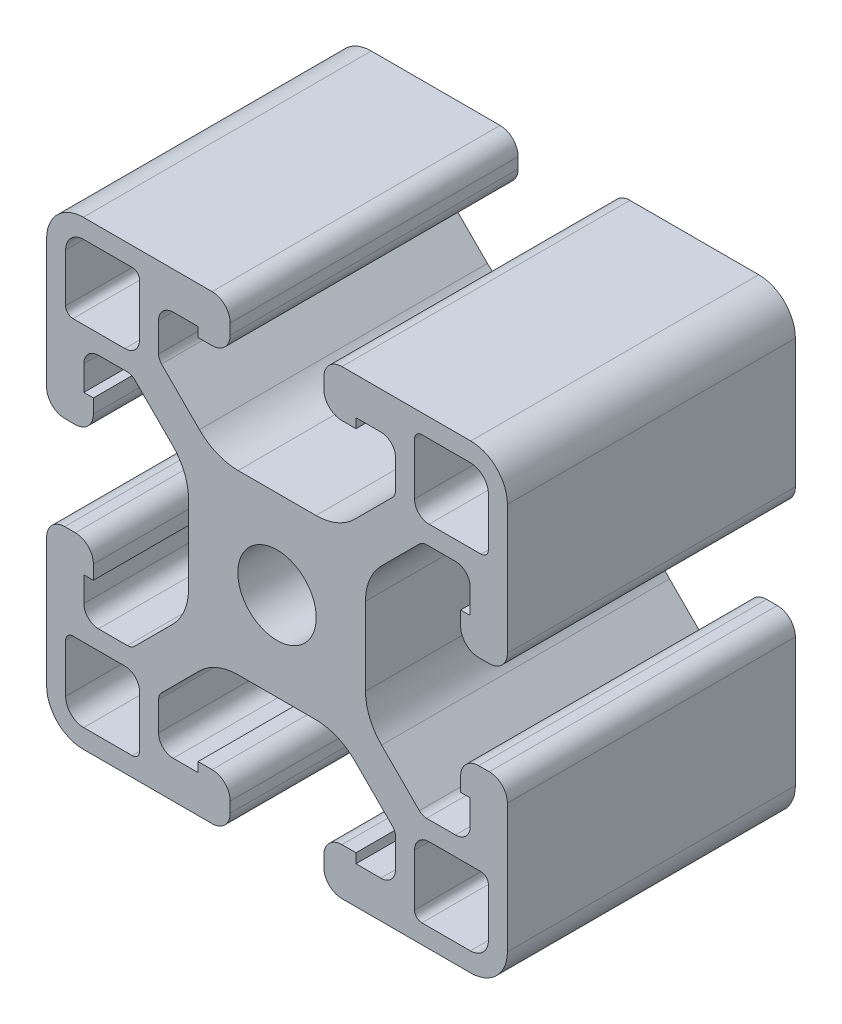
SolidWorks part; units mm, degrees
material "6005A-T61 Aluminum"
ref_plane "Front Plane" through (0, 0, 0) normal (0, 0, 1) x (1, 0, 0)
ref_plane "Top Plane" through (0, 0, 0) normal (0, 1, 0) x (1, 0, 0)
ref_plane "Right Plane" through (0, 0, 0) normal (1, 0, 0) x (0, 0, -1)
sketch "Sketch2" plane through (0, 0, 0) normal (0, 0, 1) x (1, 0, 0)
  line L0 (-16.82, 20) -> (-5.635, 20)
  line L1 (-3.379, 7.68) -> (3.379, 7.68)
  line L2 (-10.285, 12.9871) -> (-10.285, 15.5)
  line L3 (10.285, 12.9871) -> (10.285, 15.5)
  line L4 (4.065, 17.51) -> (4.065, 18.43)
  line L5 (-4.065, 17.51) -> (-4.065, 18.43)
  line L6 (-6.855, 15.94) -> (-5.635, 15.94)
  line L7 (5.635, 15.94) -> (6.855, 15.94)
  line L8 (5.635, 20) -> (16.82, 20)
  line L9 (6.855, 16.77) -> (9.015, 16.77)
  line L10 (-9.015, 16.77) -> (-6.855, 16.77)
  line L11 (-6.855, 15.94) -> (-6.855, 16.77)
  line L12 (6.855, 15.94) -> (6.855, 16.77)
  line L13 (-6.7378, 9.0712) -> (-10.0243, 12.3578)
  line L14 (6.7378, 9.0712) -> (10.0243, 12.3578)
  line L15 (-16.78, 18.35) -> (-12.575, 18.35)
  line L16 (-18.35, 16.78) -> (-18.35, 12.575)
  line L17 (-11.935, 13.205) -> (-11.935, 17.71)
  line L18 (-13.205, 11.935) -> (-17.71, 11.935)
  line L19 (-7.68, -3.379) -> (-7.68, 3.379)
  line L20 (-20, -16.82) -> (-20, -5.635)
  line L21 (-18.35, -16.78) -> (-18.35, -12.575)
  line L22 (-20, 5.635) -> (-20, 16.82)
  line L23 (-15.94, -6.855) -> (-15.94, -5.635)
  line L24 (-16.77, -9.015) -> (-16.77, -6.855)
  line L25 (-15.94, 5.635) -> (-15.94, 6.855)
  line L26 (-16.77, 6.855) -> (-16.77, 9.015)
  line L27 (-9.0712, 6.7378) -> (-12.3578, 10.0243)
  line L28 (-9.0712, -6.7378) -> (-12.3578, -10.0243)
  line L29 (-17.51, -4.065) -> (-18.43, -4.065)
  line L30 (-17.51, 4.065) -> (-18.43, 4.065)
  line L31 (-12.9871, 10.285) -> (-15.5, 10.285)
  line L32 (-15.94, 6.855) -> (-16.77, 6.855)
  line L33 (-12.9871, -10.285) -> (-15.5, -10.285)
  line L34 (-13.205, -11.935) -> (-17.71, -11.935)
  line L35 (-15.94, -6.855) -> (-16.77, -6.855)
  line L36 (-16.78, -18.35) -> (-12.575, -18.35)
  line L37 (-11.935, -13.205) -> (-11.935, -17.71)
  line L38 (3.379, -7.68) -> (-3.379, -7.68)
  line L39 (16.82, -20) -> (5.635, -20)
  line L40 (16.78, -18.35) -> (12.575, -18.35)
  line L41 (-5.635, -20) -> (-16.82, -20)
  line L42 (6.855, -15.94) -> (5.635, -15.94)
  line L43 (9.015, -16.77) -> (6.855, -16.77)
  line L44 (-5.635, -15.94) -> (-6.855, -15.94)
  line L45 (-6.855, -16.77) -> (-9.015, -16.77)
  line L46 (-6.7378, -9.0712) -> (-10.0243, -12.3578)
  line L47 (6.7378, -9.0712) -> (10.0243, -12.3578)
  line L48 (4.065, -17.51) -> (4.065, -18.43)
  line L49 (-4.065, -17.51) -> (-4.065, -18.43)
  line L50 (-10.285, -12.9871) -> (-10.285, -15.5)
  line L51 (-6.855, -15.94) -> (-6.855, -16.77)
  line L52 (10.285, -12.9871) -> (10.285, -15.5)
  line L53 (11.935, -13.205) -> (11.935, -17.71)
  line L54 (6.855, -15.94) -> (6.855, -16.77)
  line L55 (18.35, -16.78) -> (18.35, -12.575)
  line L56 (13.205, -11.935) -> (17.71, -11.935)
  line L57 (7.68, 3.379) -> (7.68, -3.379)
  line L58 (20, 16.82) -> (20, 5.635)
  line L59 (18.35, 16.78) -> (18.35, 12.575)
  line L60 (20, -5.635) -> (20, -16.82)
  line L61 (15.94, 6.855) -> (15.94, 5.635)
  line L62 (16.77, 9.015) -> (16.77, 6.855)
  line L63 (15.94, -5.635) -> (15.94, -6.855)
  line L64 (16.77, -6.855) -> (16.77, -9.015)
  line L65 (9.0712, -6.7378) -> (12.3578, -10.0243)
  line L66 (9.0712, 6.7378) -> (12.3578, 10.0243)
  line L67 (17.51, 4.065) -> (18.43, 4.065)
  line L68 (17.51, -4.065) -> (18.43, -4.065)
  line L69 (12.9871, -10.285) -> (15.5, -10.285)
  line L70 (15.94, -6.855) -> (16.77, -6.855)
  line L71 (12.9871, 10.285) -> (15.5, 10.285)
  line L72 (13.205, 11.935) -> (17.71, 11.935)
  line L73 (15.94, 6.855) -> (16.77, 6.855)
  line L74 (16.78, 18.35) -> (12.575, 18.35)
  line L75 (11.935, 13.205) -> (11.935, 17.71)
  circle A0 centre (0, 0) radius 3.405
  arc A1 (-6.7378, 9.0712) -> (-3.379, 7.68) centre (-3.379, 12.43) ccw
  arc A2 (3.379, 7.68) -> (6.7378, 9.0712) centre (3.379, 12.43) ccw
  arc A3 (10.0243, 12.3578) -> (10.285, 12.9871) centre (9.395, 12.9871) ccw
  arc A4 (-10.285, 12.9871) -> (-10.0243, 12.3578) centre (-9.395, 12.9871) ccw
  arc A5 (-9.015, 16.77) -> (-10.285, 15.5) centre (-9.015, 15.5) ccw
  arc A6 (10.285, 15.5) -> (9.015, 16.77) centre (9.015, 15.5) ccw
  arc A7 (4.065, 17.51) -> (5.635, 15.94) centre (5.635, 17.51) ccw
  arc A8 (5.635, 20) -> (4.065, 18.43) centre (5.635, 18.43) ccw
  arc A9 (-4.065, 18.43) -> (-5.635, 20) centre (-5.635, 18.43) ccw
  arc A10 (-5.635, 15.94) -> (-4.065, 17.51) centre (-5.635, 17.51) ccw
  arc A11 (-16.78, 18.35) -> (-18.35, 16.78) centre (-16.78, 16.78) ccw
  arc A12 (-11.935, 17.71) -> (-12.575, 18.35) centre (-12.575, 17.71) ccw
  arc A13 (-18.35, 12.575) -> (-17.71, 11.935) centre (-17.71, 12.575) ccw
  arc A14 (-13.205, 11.935) -> (-11.935, 13.205) centre (-13.205, 13.205) ccw
  arc A15 (-18.35, -16.78) -> (-16.78, -18.35) centre (-16.78, -16.78) ccw
  arc A16 (-20, 5.635) -> (-18.43, 4.065) centre (-18.43, 5.635) ccw
  arc A17 (-15.94, -5.635) -> (-17.51, -4.065) centre (-17.51, -5.635) ccw
  arc A18 (-16.77, -9.015) -> (-15.5, -10.285) centre (-15.5, -9.015) ccw
  arc A19 (-7.68, 3.379) -> (-9.0712, 6.7378) centre (-12.43, 3.379) ccw
  arc A20 (-9.0712, -6.7378) -> (-7.68, -3.379) centre (-12.43, -3.379) ccw
  arc A21 (-18.43, -4.065) -> (-20, -5.635) centre (-18.43, -5.635) ccw
  arc A22 (-17.51, 4.065) -> (-15.94, 5.635) centre (-17.51, 5.635) ccw
  arc A23 (-15.5, 10.285) -> (-16.77, 9.015) centre (-15.5, 9.015) ccw
  arc A24 (-12.3578, 10.0243) -> (-12.9871, 10.285) centre (-12.9871, 9.395) ccw
  arc A25 (-11.935, -13.205) -> (-13.205, -11.935) centre (-13.205, -13.205) ccw
  arc A26 (-17.71, -11.935) -> (-18.35, -12.575) centre (-17.71, -12.575) ccw
  arc A27 (-12.9871, -10.285) -> (-12.3578, -10.0243) centre (-12.9871, -9.395) ccw
  arc A28 (-12.575, -18.35) -> (-11.935, -17.71) centre (-12.575, -17.71) ccw
  arc A29 (16.78, -18.35) -> (18.35, -16.78) centre (16.78, -16.78) ccw
  arc A30 (-5.635, -20) -> (-4.065, -18.43) centre (-5.635, -18.43) ccw
  arc A31 (5.635, -15.94) -> (4.065, -17.51) centre (5.635, -17.51) ccw
  arc A32 (9.015, -16.77) -> (10.285, -15.5) centre (9.015, -15.5) ccw
  arc A33 (-3.379, -7.68) -> (-6.7378, -9.0712) centre (-3.379, -12.43) ccw
  arc A34 (6.7378, -9.0712) -> (3.379, -7.68) centre (3.379, -12.43) ccw
  arc A35 (4.065, -18.43) -> (5.635, -20) centre (5.635, -18.43) ccw
  arc A36 (-4.065, -17.51) -> (-5.635, -15.94) centre (-5.635, -17.51) ccw
  arc A37 (-10.285, -15.5) -> (-9.015, -16.77) centre (-9.015, -15.5) ccw
  arc A38 (-10.0243, -12.3578) -> (-10.285, -12.9871) centre (-9.395, -12.9871) ccw
  arc A39 (13.205, -11.935) -> (11.935, -13.205) centre (13.205, -13.205) ccw
  arc A40 (11.935, -17.71) -> (12.575, -18.35) centre (12.575, -17.71) ccw
  arc A41 (10.285, -12.9871) -> (10.0243, -12.3578) centre (9.395, -12.9871) ccw
  arc A42 (18.35, -12.575) -> (17.71, -11.935) centre (17.71, -12.575) ccw
  arc A43 (18.35, 16.78) -> (16.78, 18.35) centre (16.78, 16.78) ccw
  arc A44 (20, -5.635) -> (18.43, -4.065) centre (18.43, -5.635) ccw
  arc A45 (15.94, 5.635) -> (17.51, 4.065) centre (17.51, 5.635) ccw
  arc A46 (16.77, 9.015) -> (15.5, 10.285) centre (15.5, 9.015) ccw
  arc A47 (7.68, -3.379) -> (9.0712, -6.7378) centre (12.43, -3.379) ccw
  arc A48 (9.0712, 6.7378) -> (7.68, 3.379) centre (12.43, 3.379) ccw
  arc A49 (18.43, 4.065) -> (20, 5.635) centre (18.43, 5.635) ccw
  arc A50 (17.51, -4.065) -> (15.94, -5.635) centre (17.51, -5.635) ccw
  arc A51 (15.5, -10.285) -> (16.77, -9.015) centre (15.5, -9.015) ccw
  arc A52 (12.3578, -10.0243) -> (12.9871, -10.285) centre (12.9871, -9.395) ccw
  arc A53 (11.935, 13.205) -> (13.205, 11.935) centre (13.205, 13.205) ccw
  arc A54 (17.71, 11.935) -> (18.35, 12.575) centre (17.71, 12.575) ccw
  arc A55 (12.9871, 10.285) -> (12.3578, 10.0243) centre (12.9871, 9.395) ccw
  arc A56 (12.575, 18.35) -> (11.935, 17.71) centre (12.575, 17.71) ccw
  arc A57 (20, 16.82) -> (16.82, 20) centre (16.82, 16.82) ccw
  arc A58 (-16.82, 20) -> (-20, 16.82) centre (-16.82, 16.82) ccw
  arc A59 (-20, -16.82) -> (-16.82, -20) centre (-16.82, -16.82) ccw
  arc A60 (16.82, -20) -> (20, -16.82) centre (16.82, -16.82) ccw
extrude "Extrude1" add sketch "Sketch2" along normal mid plane 25
ref_axis "Hole RS" through (0, 0, 12.5) along (0, 0, -1)
ref_plane "Plane R" through (0, 0, 0) normal (-1, 0, 0) x (0, 0, 1)
ref_plane "Plane S" through (0, 0, 0) normal (0, 1, 0) x (1, 0, 0)
ref_plane "Left End Plane" through (0, 0, 12.5) normal (0, 0, 1) x (1, 0, 0)
ref_plane "Right End Plane" through (0, 0, -12.5) normal (0, 0, -1) x (-1, 0, 0)
